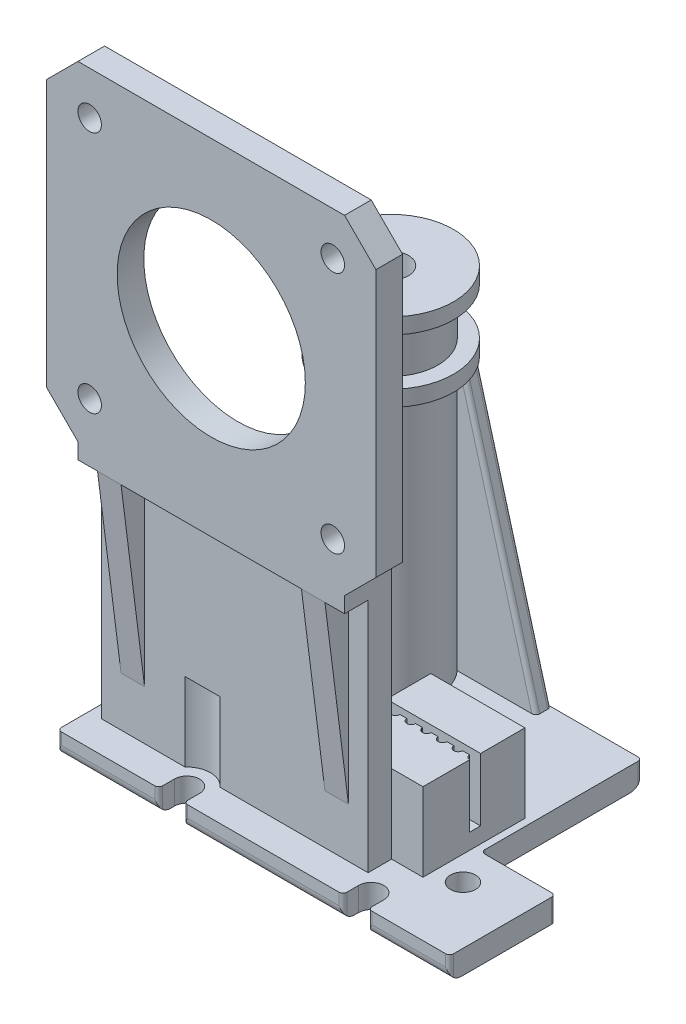
SolidWorks part; units mm, degrees
other "Markup1"
sketch "Sketch27" plane through (35.5, 79.3, -8) normal (0.5775, 0.5771, -0.5775) x (-0.7071, 0, -0.7071)
material "PET"
ref_plane "Front Plane" through (0, 0, 0) normal (0, 0, 1) x (1, 0, 0)
ref_plane "Top Plane" through (0, 0, 0) normal (0, 1, 0) x (1, 0, 0)
ref_plane "Right Plane" through (0, 0, 0) normal (1, 0, 0) x (0, 0, -1)
sketch "Sketch2" plane through (0, 0, 0) normal (0, 1, 0) x (1, 0, 0)
  line L0 (-1.6, -26.5) -> (-1.6, -28)
  line L1 (1.6, -26.5) -> (1.6, -28)
  line L2 (-14, -28.5) -> (-2.1, -28.5)
  line L3 (35.5, -28) -> (35.5, -15.5)
  line L4 (35, -15) -> (26.5, -15)
  line L5 (26, -14.5) -> (26, 5)
  line L7 (-14.5, 5) -> (-14.5, -28)
  line L10 (25.5, 5.5) -> (-14, 5.5)
  line L11 (21.9, -26.5) -> (21.9, -28)
  line L12 (25.1, -26.5) -> (25.1, -28)
  line L13 (2.1, -28.5) -> (21.4, -28.5)
  line L14 (25.6, -28.5) -> (35, -28.5)
  circle A0 centre (0, -0.5) radius 2.25
  circle A1 centre (-9, -0.5) radius 1.6
  circle A2 centre (9, -0.5) radius 1.6
  arc A3 (1.6, -26.5) -> (-1.6, -26.5) centre (0, -26.5) ccw
  circle A4 centre (10, -19.5) radius 1.6
  circle A5 centre (28.2, -19.5) radius 1.6
  arc A6 (25.1, -26.5) -> (21.9, -26.5) centre (23.5, -26.5) ccw
  arc A7 (25.1, -28) -> (25.6, -28.5) centre (25.6, -28) ccw
  arc A8 (21.9, -28) -> (21.4, -28.5) centre (21.4, -28) cw
  arc A9 (1.6, -28) -> (2.1, -28.5) centre (2.1, -28) ccw
  arc A10 (-1.6, -28) -> (-2.1, -28.5) centre (-2.1, -28) cw
  arc A11 (-14.5, -28) -> (-14, -28.5) centre (-14, -28) ccw
  arc A12 (-14, 5.5) -> (-14.5, 5) centre (-14, 5) ccw
  arc A13 (26, 5) -> (25.5, 5.5) centre (25.5, 5) ccw
  arc A14 (35, -28.5) -> (35.5, -28) centre (35, -28) ccw
  arc A15 (35.5, -15.5) -> (35, -15) centre (35, -15.5) ccw
  arc A16 (26.5, -15) -> (26, -14.5) centre (26.5, -14.5) cw
  point P29 (25.1, -28.5)
  point P32 (21.9, -28.5)
  point P35 (1.6, -28.5)
  dimension "D1" = 0.5
extrude "Boss-Extrude1" add sketch "Sketch2" along normal blind 3
fillet "Fillet1" radius 1.5 4 edges at (5.75, 0, -5.5) (-8.05, 0, 28.5) (30.3, 0, 28.5) (11.75, 0, 28.5)
sketch "Sketch5" plane through (0, 3, 0) normal (0, 1, 0) x (1, 0, 0)
  circle A0 centre (0, -0.5) radius 6
  circle A1 centre (0, -0.5) radius 2.25
extrude "Boss-Extrude3" add sketch "Sketch5" along normal blind 34.5
sketch "Sketch6" plane through (0, 37.5, 0) normal (0, 1, 0) x (1, 0, 0)
  circle A0 centre (0, -0.5) radius 8
  circle A1 centre (0, -0.5) radius 2.25
extrude "Boss-Extrude4" add sketch "Sketch6" along normal blind 2
sketch "Sketch7" plane through (0, 39.5, 0) normal (0, 1, 0) x (1, 0, 0)
  circle A0 centre (0, -0.5) radius 2.25
  circle A1 centre (0, -0.5) radius 6
extrude "Boss-Extrude5" add sketch "Sketch7" along normal blind 6
sketch "Sketch13" plane through (0, 3, 0) normal (0, 1, 0) x (1, 0, 0)
  line L1 (-12.9, -21.5) -> (21.1, -21.5)
  line L4 (-12.9, -21.5) -> (-12.9, -24.5)
  line L8 (-12.9, -24.5) -> (21.1, -24.5)
  line L9 (21.1, -21.5) -> (21.1, -24.5)
extrude "Boss-Extrude8" add sketch "Sketch13" along normal blind 30.1
sketch "Sketch16" plane through (0, 33.1, 0) normal (0, 1, 0) x (1, 0, 0)
  line L2 (-12.9, -21.5) -> (-12.9, -27.5)
  line L3 (21.1, -21.5) -> (21.1, -27.5)
  line L4 (21.1, -27.5) -> (-12.9, -27.5)
  line L11 (21.1, -21.5) -> (-12.9, -21.5)
extrude "Boss-Extrude10" add sketch "Sketch16" along normal blind 2
sketch "Sketch17" plane through (0, 0, 24.5) normal (0, 0, 1) x (1, 0, 0)
  line L1 (-10.4, 33.1) -> (-7.4, 33.1)
  line L2 (-10.4, 33.1) -> (-10.4, 9.3)
  line L3 (-10.4, 9.3) -> (-7.4, 9.3)
  line L4 (-7.4, 33.1) -> (-7.4, 9.3)
  line L5 (18.6, 33.1) -> (15.6, 33.1)
  line L6 (18.6, 33.1) -> (18.6, 9.3)
  line L7 (18.6, 9.3) -> (15.6, 9.3)
  line L8 (15.6, 33.1) -> (15.6, 9.3)
extrude "Boss-Extrude11" add sketch "Sketch17" along normal up to surface (3 mm away) up to face at (4.1, 34.1, 27.5)
sketch "Sketch18" plane through (-10.4, 0, 0) normal (-1, 0, 0) x (0, 0, 1)
  line L0 (24.5, 9.3) -> (27.5, 33.1)
  line L1 (27.5, 33.1) -> (27.5, 9.3)
  line L2 (27.5, 9.3) -> (24.5, 9.3)
extrude "Cut-Extrude5" cut sketch "Sketch18" against normal up to surface (31.5 mm away) up to face at (21.1, 23.7333, 24.5)
sketch "Sketch19" plane through (0, 35.1, 0) normal (0, 1, 0) x (1, 0, 0)
  line L1 (-16.9, -24.1) -> (25.1, -24.1)
  line L8 (-16.9, -24.1) -> (-16.9, -27.5)
  line L9 (-16.9, -27.5) -> (25.1, -27.5)
  line L10 (25.1, -27.5) -> (25.1, -24.1)
extrude "Boss-Extrude12" add sketch "Sketch19" along normal blind 42
sketch "Sketch21" plane through (0, 0, 27.5) normal (0, 0, 1) x (1, 0, 0)
  line L0 (-16.9, 77.1) -> (-12.9, 77.1)
  line L3 (25.1, 77.1) -> (25.1, 73.1)
  line L5 (25.1, 73.1) -> (21.1, 77.1)
  line L7 (-12.9, 77.1) -> (-16.9, 73.1)
  line L9 (-16.9, 73.1) -> (-16.9, 77.1)
  line L12 (21.1, 77.1) -> (25.1, 77.1)
  line L15 (25.1, 35.1) -> (21.1, 35.1)
  line L21 (21.1, 35.1) -> (25.1, 39.1)
  line L23 (25.1, 39.1) -> (25.1, 35.1)
  line L24 (-16.9, 35.1) -> (-12.9, 35.1)
  line L26 (-12.9, 35.1) -> (-16.9, 39.1)
  line L28 (-16.9, 39.1) -> (-16.9, 35.1)
  circle A0 centre (4.1, 56.1) radius 12
  circle A1 centre (-11.4, 71.6) radius 1.5
  circle A2 centre (19.6, 40.6) radius 1.5
  circle A4 centre (19.6, 71.6) radius 1.5
  circle A5 centre (-11.4, 40.6) radius 1.5
extrude "Cut-Extrude6" cut sketch "Sketch21" against normal up to surface (3.4 mm away) up to face at (4.1, 49.1, 24.1)
sketch "Sketch28" plane through (0, 45.5, 0) normal (0, 1, 0) x (1, 0, 0)
  circle A0 centre (0, -0.5) radius 2.25
  circle A1 centre (0, -0.5) radius 8
extrude "Boss-Extrude19" add sketch "Sketch28" along normal blind 2
sketch "Sketch29" plane through (0, 0, -5.5) normal (0, 0, -1) x (-1, 0, 0)
  line L0 (14.5, 3) -> (-14.5, 3)
  line L6 (-14.5, 3) -> (-5, 37.5)
  line L7 (-5, 37.5) -> (5, 37.5)
  line L8 (5, 37.5) -> (14.5, 3)
extrude "Boss-Extrude20" add sketch "Sketch29" against normal blind 2
fillet "Fillet4" radius 0.5 4 edges at (9.75, 20.25, -3.5) (-9.75, 20.25, -3.5) (-9.75, 20.25, -5.5) (9.75, 20.25, -5.5)
sketch "Sketch30" plane through (0, 3, 0) normal (0, 1, 0) x (1, 0, 0)
  line L1 (25.1, -8.5) -> (13.1, -8.5)
  line L4 (13.1, -21.5) -> (25.1, -21.5)
  line L5 (13.1, -21.5) -> (13.1, -8.5)
  line L7 (25.1, -21.5) -> (25.1, -8.5)
extrude "Boss-Extrude23" add sketch "Sketch30" along normal blind 10
sketch "Sketch4" plane through (0, 13, 0) normal (0, 1, 0) x (1, 0, 0)
  line L0 (24.545, -15) -> (23.655, -15)
  line L1 (22.545, -15) -> (21.655, -15)
  line L2 (20.545, -15) -> (19.655, -15)
  line L3 (18.545, -15) -> (17.655, -15)
  line L4 (13.1, -14.155) -> (25.1, -14.155)
  line L5 (25.1, -14.155) -> (25.1, -15.555)
  line L6 (13.1, -14.155) -> (13.1, -15.555)
  line L7 (16.545, -15) -> (15.655, -15)
  line L8 (14.545, -15) -> (13.655, -15)
  arc A0 (22.545, -15) -> (23.655, -15) centre (23.1, -15) ccw
  arc A1 (24.545, -15) -> (25.1, -15.555) centre (25.1, -15) ccw
  arc A2 (20.545, -15) -> (21.655, -15) centre (21.1, -15) ccw
  arc A3 (19.655, -15) -> (18.545, -15) centre (19.1, -15) cw
  arc A5 (17.655, -15) -> (16.545, -15) centre (17.1, -15) cw
  arc A8 (14.545, -15) -> (15.655, -15) centre (15.1, -15) ccw
  arc A9 (13.655, -15) -> (13.1, -15.555) centre (13.1, -15) cw
extrude "Cut-Extrude7" cut sketch "Sketch4" against normal blind 8
sketch "Sketch14" plane through (0, 3, 0) normal (0, 1, 0) x (1, 0, 0)
  circle A0 centre (-9, -0.5) radius 3
  circle A1 centre (9, -0.5) radius 3
  circle A2 centre (10, -19.5) radius 3
  circle A3 centre (0, -26.5) radius 3
  circle A4 centre (28.2, -19.5) radius 3
  circle A5 centre (23.5, -26.5) radius 3
extrude "Cut-Extrude9" cut sketch "Sketch14" along normal blind 10
sketch "Sketch32" plane through (0, 3, 0) normal (0, 1, 0) x (1, 0, 0)
  line L10 (-14.5, -8.5) -> (6.9, -8.5)
  line L11 (-14.5, -8.5) -> (-14.5, -21.5)
  line L12 (-14.5, -21.5) -> (6.9, -21.5)
  line L13 (6.9, -8.5) -> (6.9, -21.5)
extrude "Boss-Extrude24" add sketch "Sketch32" along normal blind 2
sketch "Sketch33" plane through (-14.5, 0, 0) normal (-1, 0, 0) x (0, 0, 1)
  line L5 (11.5, 3) -> (12, 5)
  line L6 (12, 5) -> (18, 5)
  line L7 (18, 5) -> (18.5, 3)
  line L8 (18.5, 3) -> (11.5, 3)
  point P0 (0, 0)
extrude "Cut-Extrude10" cut sketch "Sketch33" against normal up to surface (21.4 mm away) up to face at (6.9, 4, 15)
fillet "Fillet5" radius 0.5 4 edges at (6.9, 4, 11.75) (6.9, 4, 18.25) (-14.5, 4, 18.25) (-14.5, 4, 11.75)
equation "\"ё\"=10"
